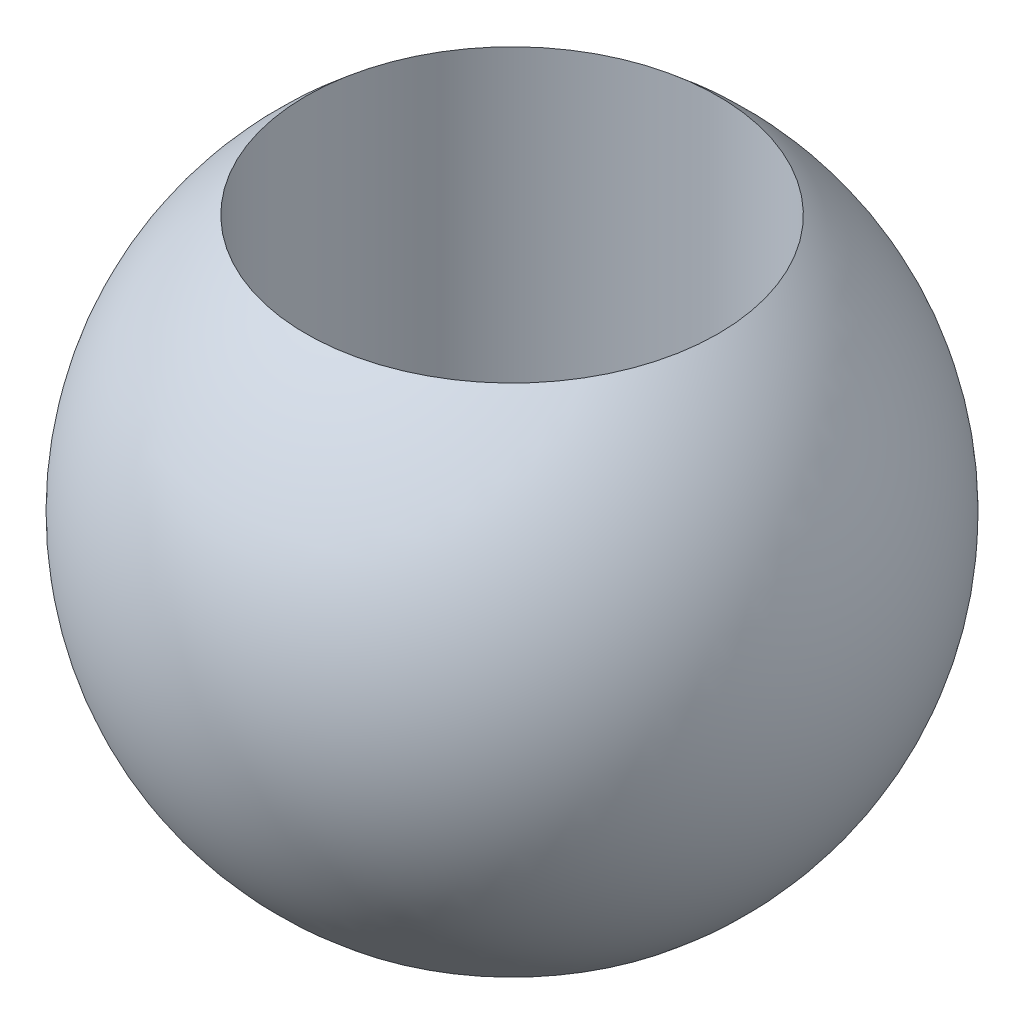
SolidWorks part; units mm, degrees
ref_plane "Front Plane" through (0, 0, 0) normal (0, 0, 1) x (1, 0, 0)
ref_plane "Top Plane" through (0, 0, 0) normal (0, 1, 0) x (1, 0, 0)
ref_plane "Right Plane" through (0, 0, 0) normal (1, 0, 0) x (0, 0, -1)
sketch "Sketch1" plane through (0, 0, 0) normal (0, 0, 1) x (1, 0, 0)
  line L0 (0, 2.54) -> (0, -2.54)
  line L1 (1.5875, 2.803) -> (1.5875, -2.9729)
  arc A0 (0, 2.54) -> (0, -2.54) centre (0, 0) cw
  point P4 (0, 0)
  dimension "D1" = 2.54
  dimension "D2" = 1.5875
revolve "Revolve1" add sketch "Sketch1" angle 360 about L0 region at (1.9754, 0, 0)
